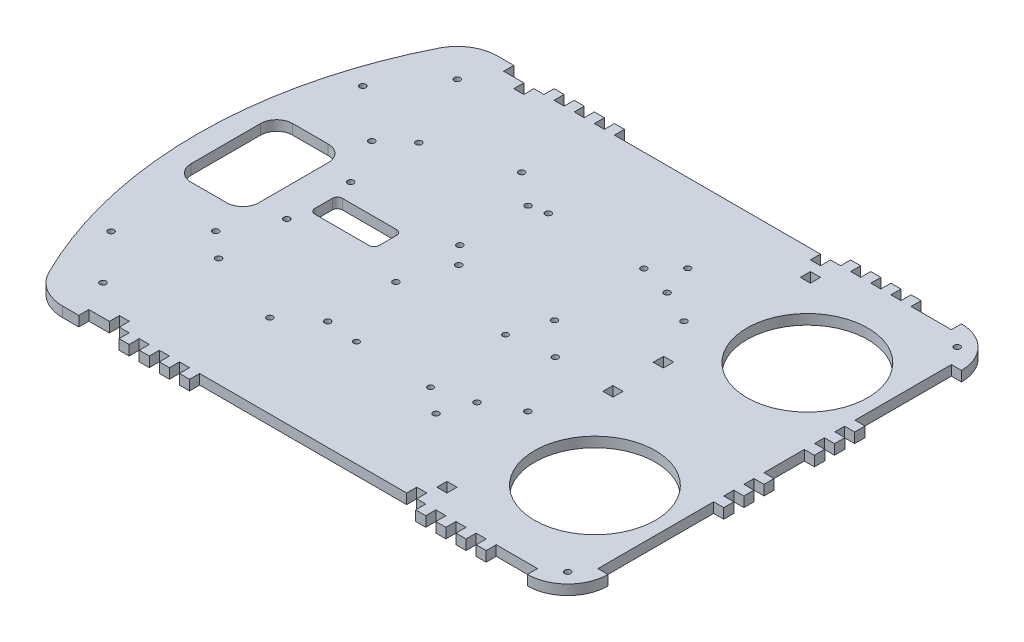
SolidWorks part; units mm, degrees
ref_plane "Front Plane" through (0, 0, 0) normal (0, 0, 1) x (1, 0, 0)
ref_plane "Top Plane" through (0, 0, 0) normal (0, 1, 0) x (1, 0, 0)
ref_plane "Right Plane" through (0, 0, 0) normal (1, 0, 0) x (0, 0, -1)
sketch "main_base_sketch" plane through (0, 0, 0) normal (0, 1, 0) x (1, 0, 0)
  line L1 (111.125, 92.7285) -> (111.125, 23.3533) construction
  line L2 (111.125, -38.1761) -> (111.125, 0) construction
  line L3 (111.125, -99.4864) -> (111.125, -136.4602) construction
  line L5 (111.125, 23.3533) -> (111.125, 0) construction
  line L7 (111.125, 92.7285) -> (111.125, 23.3533) construction
  line L9 (111.125, 0) -> (111.125, 23.3533) construction
  line L10 (111.125, 0) -> (111.125, -38.1761) construction
  line L11 (111.125, 0) -> (111.125, -38.1761) construction
  line L20 (-111.125, 0) -> (111.125, 0) construction
  line L22 (111.125, 130.8285) -> (117.475, 130.8285) construction
  line L24 (-94.9614, 130.8285) -> (-94.9614, 124.4785) construction
  line L25 (-94.9614, 124.4785) -> (-82.2614, 124.4785)
  line L26 (187.325, 130.8285) -> (187.325, 124.4785)
  line L27 (-95.6016, -142.8102) -> (111.125, -142.8102) construction
  line L28 (-95.6016, -142.8102) -> (-95.6016, -136.4602)
  line L29 (-95.6016, -136.4602) -> (-82.6643, -136.4602)
  line L30 (187.325, -142.8102) -> (187.325, -136.4602)
  line L32 (-94.9614, 130.8285) -> (-25.1114, 130.8285) construction
  line L33 (111.125, -142.8102) -> (187.325, -142.8102) construction
  line L34 (111.125, -136.4602) -> (111.125, -142.8102) construction
  line L36 (111.125, -136.4602) -> (111.125, -142.8102) construction
  line L37 (-56.8614, 130.8285) -> (-50.5114, 130.8285)
  line L38 (111.125, 12.7) -> (117.4276, 12.7)
  line L52 (111.125, 12.7) -> (111.125, 19.2555)
  line L53 (111.125, 23.3533) -> (111.125, 0) construction
  line L54 (111.125, 19.2555) -> (117.4276, 19.2555)
  line L55 (-94.9614, 130.8285) -> (-25.1114, 130.8285) construction
  line L58 (111.125, 124.4785) -> (111.125, 92.7285) construction
  line L61 (-95.6016, -142.8102) -> (111.125, -142.8102) construction
  line L62 (111.125, -99.4864) -> (111.125, -136.4602) construction
  line L63 (111.125, 130.8285) -> (117.475, 130.8285) construction
  line L64 (111.125, 124.4785) -> (111.125, 92.7285) construction
  line L65 (111.125, -142.8102) -> (187.325, -142.8102) construction
  line L66 (212.725, 105.4285) -> (212.725, -117.4102) construction
  line L67 (117.4276, 12.7) -> (117.4276, 19.2555)
  line L68 (111.125, -12.7) -> (117.475, -12.7)
  line L69 (111.125, -12.7) -> (111.125, -19.05)
  line L70 (111.125, -19.05) -> (117.475, -19.05)
  line L71 (117.475, -12.7) -> (117.475, -19.05)
  line L72 (111.125, 105.4285) -> (117.475, 105.4285)
  line L73 (111.125, 105.4285) -> (111.125, 111.7785)
  line L74 (111.125, 111.7785) -> (117.475, 111.7785)
  line L75 (117.475, 105.4285) -> (117.475, 111.7785)
  line L76 (111.125, -117.4102) -> (117.475, -117.4102)
  line L77 (111.125, -117.4102) -> (111.125, -123.7602)
  line L78 (111.125, -123.7602) -> (117.475, -123.7602)
  line L79 (117.475, -117.4102) -> (117.475, -123.7602)
  line L80 (212.725, 105.4285) -> (206.375, 105.4285)
  line L81 (212.725, 105.4285) -> (212.725, -117.4102) construction
  line L82 (212.725, -117.4102) -> (206.375, -117.4102)
  line L84 (-69.5614, 130.8285) -> (-63.2114, 130.8285)
  line L85 (-69.5614, 130.8285) -> (-69.5614, 124.4785)
  line L86 (-69.5614, 124.4785) -> (-63.2114, 124.4785) construction
  line L87 (-63.2114, 130.8285) -> (-63.2114, 124.4785)
  line L88 (-56.8614, 130.8285) -> (-56.8614, 124.4785)
  line L89 (-56.8614, 124.4785) -> (-50.5114, 124.4785) construction
  line L90 (-50.5114, 130.8285) -> (-50.5114, 124.4785)
  line L91 (-44.1614, 130.8285) -> (-37.8114, 130.8285)
  line L92 (-44.1614, 130.8285) -> (-44.1614, 124.4785)
  line L93 (-44.1614, 124.4785) -> (-37.8114, 124.4785) construction
  line L94 (-37.8114, 130.8285) -> (-37.8114, 124.4785)
  line L95 (-31.4614, 130.8285) -> (-25.1114, 130.8285)
  line L96 (-31.4614, 130.8285) -> (-31.4614, 124.4785)
  line L97 (-31.4614, 124.4785) -> (-25.1114, 124.4785) construction
  line L98 (-25.1114, 130.8285) -> (-25.1114, 124.4785)
  line L99 (-69.5614, 124.4785) -> (-63.2114, 124.4785) construction
  line L100 (-63.2114, 124.4785) -> (-56.8614, 124.4785)
  line L101 (-56.8614, 124.4785) -> (-50.5114, 124.4785) construction
  line L102 (-50.5114, 124.4785) -> (-44.1614, 124.4785)
  line L103 (-44.1614, 124.4785) -> (-37.8114, 124.4785) construction
  line L104 (-37.8114, 124.4785) -> (-31.4614, 124.4785)
  line L105 (-31.4614, 124.4785) -> (-25.1114, 124.4785) construction
  line L106 (-25.1114, 124.4785) -> (104.775, 124.4785)
  line L107 (149.225, 130.8285) -> (142.875, 130.8285)
  line L108 (161.925, 130.8285) -> (155.575, 130.8285)
  line L109 (161.925, 130.8285) -> (161.925, 124.4785)
  line L110 (161.925, 124.4785) -> (155.575, 124.4785) construction
  line L111 (155.575, 130.8285) -> (155.575, 124.4785)
  line L112 (149.225, 130.8285) -> (149.225, 124.4785)
  line L114 (142.875, 130.8285) -> (142.875, 124.4785)
  line L115 (136.525, 130.8285) -> (130.175, 130.8285)
  line L116 (136.525, 130.8285) -> (136.525, 124.4785)
  line L118 (130.175, 130.8285) -> (130.175, 124.4785)
  line L119 (123.825, 130.8285) -> (117.475, 130.8285) construction
  line L120 (123.825, 130.8285) -> (123.825, 124.4785)
  line L122 (117.475, 130.8285) -> (117.475, 124.4785) construction
  line L123 (117.475, 130.8285) -> (123.825, 130.8285) construction
  line L124 (206.375, 105.4285) -> (206.375, 44.6555)
  line L127 (117.475, 130.8285) -> (117.475, 124.4785) construction
  line L128 (117.475, 130.8285) -> (117.475, 124.4785) construction
  line L129 (145.8534, 124.4785) -> (130.175, 124.4785) [skipped]
  line L130 (149.225, 124.4785) -> (146.7264, 124.4785) [skipped]
  line L131 (123.825, 124.4785) -> (130.175, 124.4785)
  line L132 (136.525, 124.4785) -> (142.875, 124.4785)
  line L133 (149.225, 124.4785) -> (155.575, 124.4785)
  line L134 (161.925, 124.4785) -> (187.325, 124.4785)
  line L135 (133.0367, 124.4785) -> (117.475, 124.4785) [skipped]
  line L136 (123.825, 130.8285) -> (187.325, 130.8285) construction
  line L137 (117.475, 130.8285) -> (123.825, 130.8285) construction
  line L138 (123.825, 130.8285) -> (187.325, 130.8285) construction
  line L139 (-25.1114, 130.8285) -> (111.125, 130.8285) construction
  line L140 (-25.1114, 130.8285) -> (111.125, 130.8285) construction
  line L141 (111.125, 130.8285) -> (111.125, 124.4785) construction
  line L142 (111.125, 130.8285) -> (111.125, 124.4785) construction
  line L143 (123.825, 130.8285) -> (117.475, 130.8285)
  line L144 (117.475, 130.8285) -> (117.475, 124.4785)
  line L151 (206.375, -12.7) -> (212.725, -12.7)
  line L152 (206.375, -12.7) -> (206.375, -19.05) construction
  line L153 (206.375, -19.05) -> (212.725, -19.05)
  line L154 (212.725, -12.7) -> (212.725, -19.05)
  line L155 (206.375, -12.7) -> (206.375, -19.05) construction
  line L156 (206.375, -19.05) -> (206.375, -25.4)
  line L157 (206.375, 19.2555) -> (212.725, 19.2555)
  line L158 (212.725, 19.2555) -> (212.725, 12.7)
  line L159 (212.725, 12.7) -> (206.375, 12.7)
  line L160 (206.375, 24.1792) -> (206.375, 19.2555)
  line L161 (206.375, 12.7) -> (206.375, -12.7)
  line L162 (-70.2016, -136.4602) -> (-70.2016, -142.8102)
  line L163 (-70.2016, -142.8102) -> (-63.8516, -142.8102)
  line L164 (-63.8516, -142.8102) -> (-63.8516, -136.4602)
  line L165 (-70.2016, -136.4602) -> (-63.8516, -136.4602) construction
  line L166 (-63.8516, -136.4602) -> (-57.5016, -136.4602)
  line L167 (-57.5016, -142.8102) -> (-51.1516, -142.8102)
  line L168 (-57.5016, -136.4602) -> (-57.5016, -142.8102)
  line L169 (-51.1516, -142.8102) -> (-51.1516, -136.4602)
  line L170 (-44.8016, -142.8102) -> (-38.4516, -142.8102)
  line L171 (-44.8016, -136.4602) -> (-44.8016, -142.8102)
  line L172 (-38.4516, -142.8102) -> (-38.4516, -136.4602)
  line L173 (-32.1016, -142.8102) -> (-25.7516, -142.8102)
  line L174 (-32.1016, -136.4602) -> (-32.1016, -142.8102)
  line L175 (-25.7516, -142.8102) -> (-25.7516, -136.4602)
  line L176 (-57.5016, -136.4602) -> (-51.1516, -136.4602) construction
  line L177 (-51.1516, -136.4602) -> (-44.8016, -136.4602)
  line L178 (-44.8016, -136.4602) -> (-38.4516, -136.4602) construction
  line L179 (-38.4516, -136.4602) -> (-32.1016, -136.4602)
  line L180 (-32.1016, -136.4602) -> (-25.7516, -136.4602) construction
  line L181 (-25.7516, -136.4602) -> (104.775, -136.4602)
  line L182 (161.2847, -136.4602) -> (161.2847, -142.8102)
  line L183 (161.2847, -142.8102) -> (154.9347, -142.8102)
  line L184 (154.9347, -142.8102) -> (154.9347, -136.4602)
  line L185 (148.5847, -136.4602) -> (148.5847, -142.8102)
  line L186 (148.5847, -142.8102) -> (142.2347, -142.8102)
  line L187 (142.2347, -142.8102) -> (142.2347, -136.4602)
  line L188 (135.8847, -136.4602) -> (135.8847, -142.8102)
  line L189 (135.8847, -142.8102) -> (129.5347, -142.8102)
  line L190 (129.5347, -142.8102) -> (129.5347, -136.4602)
  line L191 (123.1847, -136.4602) -> (123.1847, -142.8102)
  line L192 (123.1847, -142.8102) -> (116.8347, -142.8102)
  line L193 (116.8347, -142.8102) -> (116.8347, -136.4602)
  line L194 (154.9347, -136.4602) -> (161.2847, -136.4602) construction
  line L195 (161.2847, -136.4602) -> (187.325, -136.4602)
  line L196 (142.2347, -136.4602) -> (148.5847, -136.4602) construction
  line L197 (148.5847, -136.4602) -> (154.9347, -136.4602)
  line L198 (129.5347, -136.4602) -> (135.8847, -136.4602) construction
  line L199 (135.8847, -136.4602) -> (142.2347, -136.4602)
  line L200 (116.8347, -136.4602) -> (123.1847, -136.4602) construction
  line L201 (123.1847, -136.4602) -> (129.5347, -136.4602)
  line L202 (212.725, 25.4) -> (206.375, 25.4)
  line L203 (212.725, 31.9555) -> (212.725, 25.4)
  line L204 (206.375, 31.9555) -> (212.725, 31.9555)
  line L205 (212.725, 38.1) -> (206.375, 38.1)
  line L206 (212.725, 44.6555) -> (212.725, 38.1)
  line L207 (206.375, 44.6555) -> (212.725, 44.6555)
  line L208 (206.375, 31.9555) -> (206.375, 25.4) construction
  line L209 (206.375, 25.4) -> (206.375, 24.1792)
  line L210 (206.375, 44.6555) -> (206.375, 38.1) construction
  line L211 (206.375, 38.1) -> (206.375, 31.9555)
  line L212 (206.375, -31.75) -> (212.725, -31.75)
  line L213 (212.725, -25.4) -> (212.725, -31.75)
  line L214 (206.375, -25.4) -> (212.725, -25.4)
  line L215 (206.375, -44.45) -> (212.725, -44.45)
  line L216 (212.725, -38.1) -> (212.725, -44.45)
  line L217 (206.375, -38.1) -> (212.725, -38.1)
  line L218 (206.375, -25.4) -> (206.375, -31.75) construction
  line L219 (206.375, -31.75) -> (206.375, -38.1)
  line L220 (206.375, -38.1) -> (206.375, -44.45) construction
  line L221 (206.375, -44.45) -> (206.375, -117.4102)
  line L225 (-95.5505, 130.8285) -> (-157.7358, 130.8285) construction
  line L229 (-132.8963, 29.3852) -> (-110.4973, 29.3852)
  line L230 (-143.0563, 19.2252) -> (-143.0563, -24.5291)
  line L231 (-132.8963, -34.6891) -> (-110.4973, -34.6891)
  line L238 (-100.3373, 19.2252) -> (-100.3373, -24.5291)
  line L248 (-94.9614, 130.8285) -> (-95.5505, 130.8285) construction
  line L254 (-94.9614, 130.8285) -> (-95.5505, 130.8285) construction
  line L257 (-94.9614, 130.8285) -> (-105.2412, 130.8285)
  line L258 (-95.5505, 130.8285) -> (-94.9614, 130.8285) construction
  line L259 (-95.6016, -142.8102) -> (-105.7982, -142.8102)
  line L260 (-94.9614, 124.4785) -> (-94.9614, 130.8285)
  line L261 (-94.9614, 130.8285) -> (-95.5505, 130.8285) construction
  line L262 (-82.2614, 124.4785) -> (-75.9114, 124.4785) construction
  line L263 (-82.2614, 124.4785) -> (-75.9114, 124.4785) construction
  line L264 (-82.2614, 124.4785) -> (-82.2614, 118.1285)
  line L265 (-82.2614, 118.1285) -> (-75.9114, 118.1285)
  line L266 (-75.9114, 124.4785) -> (-75.9114, 118.1285)
  line L267 (-97.1554, -142.8102) -> (-95.6016, -142.8102) construction
  line L269 (-75.9114, 124.4785) -> (-69.5614, 124.4785)
  line L270 (104.775, 124.4785) -> (111.125, 124.4785) construction
  line L271 (111.125, 124.4785) -> (104.775, 124.4785) construction
  line L272 (111.125, 124.4785) -> (111.125, 118.1285)
  line L274 (111.125, 118.1285) -> (104.775, 118.1285)
  line L280 (104.775, 124.4785) -> (104.775, 118.1285)
  line L281 (111.125, 124.4785) -> (117.475, 124.4785)
  line L282 (104.775, -136.4602) -> (111.125, -136.4602) construction
  line L285 (111.125, -136.4602) -> (104.775, -136.4602) construction
  line L286 (111.125, -136.4602) -> (111.125, -130.1018)
  line L289 (111.125, -130.1018) -> (104.775, -130.1018)
  line L291 (104.775, -136.4602) -> (104.775, -130.1018)
  line L292 (111.125, -136.4602) -> (116.8347, -136.4602)
  line L293 (-82.6643, -136.4602) -> (-76.4089, -136.4602) construction
  line L294 (-94.9614, 130.8285) -> (-95.5505, 130.8285) construction
  line L295 (-157.7358, 130.8285) -> (-157.7358, -142.8102) construction
  line L296 (-157.7358, -142.8102) -> (-97.1554, -142.8102) construction
  line L297 (-95.5505, 130.8285) -> (-157.7358, 130.8285) construction
  line L298 (-82.6643, -136.4602) -> (-76.4089, -136.4602) construction
  line L299 (-82.6643, -136.4602) -> (-82.6643, -130.1018)
  line L300 (-82.6643, -130.1018) -> (-76.4089, -130.1018)
  line L301 (-76.4089, -136.4602) -> (-76.4089, -130.1018)
  line L302 (-76.4089, -136.4602) -> (-70.2016, -136.4602)
  arc A34 (212.725, -117.4102) -> (187.325, -142.8102) centre (187.325, -117.4102) cw
  arc A35 (212.725, 105.4285) -> (187.325, 130.8285) centre (187.325, 105.4285) ccw
  circle A37 centre (160.02, 60.9785) radius 38.1
  circle A38 centre (160.02, -72.9602) radius 38.1
  arc A41 (-127.9188, 116.8691) -> (-128.5327, -128.7374) centre (116.7138, -6.5464) ccw
  arc A42 (-127.9188, 116.8691) -> (-105.2412, 130.8285) centre (-105.2412, 105.4285) cw
  arc A43 (-128.5327, -128.7374) -> (-105.7982, -142.8102) centre (-105.7982, -117.4102) ccw
  circle A44 centre (-131.2964, 71.9636) radius 1.905
  circle A45 centre (-131.2964, -86.7864) radius 1.905
  circle A46 centre (198.6177, 116.8691) radius 1.905
  circle A47 centre (198.6177, -128.7374) radius 1.905
  circle A50 centre (-105.2412, 105.4285) radius 1.905
  arc A51 (-110.4973, -34.6891) -> (-100.3373, -24.5291) centre (-110.4973, -24.5291) ccw
  arc A52 (-143.0563, -24.5291) -> (-132.8963, -34.6891) centre (-132.8963, -24.5291) ccw
  arc A53 (-132.8963, 29.3852) -> (-143.0563, 19.2252) centre (-132.8963, 19.2252) ccw
  arc A54 (-110.4973, 29.3852) -> (-100.3373, 19.2252) centre (-110.4973, 19.2252) cw
  circle A55 centre (-105.7982, -117.4102) radius 1.905
  point P16 (-120.3614, 130.8285)
  point P19 (212.725, -142.8102)
  point P46 (-121.0016, -142.8102)
  point P123 (0, 0)
  dimension "D7" = 63.5
  dimension "D12" = 25.4
  dimension "D13" = 25.4
  dimension "D21" = 63.5
  dimension "D24" = 76.2
  dimension "D26" = 76.2
  dimension "D14" = 25.4
  dimension "D30" = 3.81
  dimension "D31" = 6.35
  dimension "D4" = 10.16
  dimension "D8" = 4
  dimension "D11" = 4
  dimension "D19" = 6.35
  dimension "D20" = 6.35
  dimension "D27" = 10.2799
  dimension "D28" = 10.1966
  dimension "D29" = 6.5555
  dimension "D32" = 6.35
  dimension "D33" = 6.35
  dimension "D36" = 6.35
  dimension "D57" = 38.1
  dimension "D58" = 6.35
  dimension "D59" = 101.6
  dimension "D60" = 6.3026
  dimension "D61" = 12.7
  dimension "D62" = 12.7
  dimension "D63" = 6.35
  dimension "D64" = 6.35
  dimension "D65" = 6.35
  dimension "D66" = 6.35
  dimension "D67" = 12.7
  dimension "D68" = 12.7
  dimension "D69" = 6.35
  dimension "D70" = 6.35
  dimension "D71" = 4
  dimension "D72" = 6.35
  dimension "D73" = 6.35
  dimension "D74" = 6.35
  dimension "D76" = 3
  dimension "D77" = 3
  dimension "D78" = 6.3585
  dimension "D79" = 282.9266
  dimension "D75" = 4
extrude "main_base" add sketch "main_base_sketch" along normal blind 6.35
sketch "Sketch1" plane through (0, 6.35, 0) normal (0, 1, 0) x (1, 0, 0)
  line L20 (-111.125, -4.4655) -> (111.125, -4.4655) construction
  line L39 (-42.259, -13.1472) -> (-76.4089, -13.1472)
  line L40 (-39.084, -9.9722) -> (-39.084, 1.0411)
  line L41 (-42.259, 4.2161) -> (-76.4089, 4.2161)
  line L42 (-79.5839, -9.9722) -> (-79.5839, 1.0411)
  line L43 (-39.084, -13.1472) -> (-79.5839, 4.2161) construction
  line L44 (-39.084, 4.2161) -> (-79.5839, -13.1472) construction
  line L45 (61.595, 59.0345) -> (93.345, 59.0345) construction
  line L46 (61.595, 59.0345) -> (61.595, -67.9655) construction
  line L47 (61.595, -67.9655) -> (93.345, -67.9655) construction
  line L48 (93.345, 59.0345) -> (93.345, -67.9655) construction
  line L49 (61.595, 59.0345) -> (93.345, -67.9655) construction
  line L50 (61.595, -67.9655) -> (93.345, 59.0345) construction
  circle A0 centre (-82.6643, 58.6916) radius 1.905
  circle A1 centre (-13.8303, 58.6916) radius 1.905
  arc A2 (-76.4089, -13.1472) -> (-79.5839, -9.9722) centre (-76.4089, -9.9722) cw
  arc A3 (-42.259, -13.1472) -> (-39.084, -9.9722) centre (-42.259, -9.9722) ccw
  arc A4 (-39.084, 1.0411) -> (-42.259, 4.2161) centre (-42.259, 1.0411) ccw
  arc A5 (-76.4089, 4.2161) -> (-79.5839, 1.0411) centre (-76.4089, 1.0411) ccw
  circle A10 centre (-3.2843, 60.9395) radius 1.905
  circle A11 centre (-13.8303, 15.6894) radius 1.905
  circle A12 centre (-3.2843, 4.4753) radius 1.905
  circle A13 centre (-82.6643, 15.6894) radius 1.905
  circle A14 centre (-82.6643, -24.6204) radius 1.905
  circle A15 centre (-13.8303, -24.6204) radius 1.905
  circle A16 centre (-82.6643, -67.6226) radius 1.905
  circle A17 centre (-13.8303, -67.6226) radius 1.905
  circle A18 centre (6.29, -69.6017) radius 1.796
  circle A19 centre (54.55, -71.1892) radius 1.796
  circle A20 centre (49.47, -18.8017) radius 1.796
  circle A21 centre (57.0407, 4.4753) radius 1.905
  circle A22 centre (57.0407, 60.9395) radius 1.905
  circle A23 centre (-98.425, 44.7683) radius 1.905
  circle A24 centre (-34.0871, 74.9095) radius 1.905
  circle A25 centre (70.6863, 74.9095) radius 1.905
  circle A26 centre (98.425, 44.7683) radius 1.905
  circle A27 centre (98.425, -53.6993) radius 1.905
  circle A28 centre (70.6863, -83.8405) radius 1.905
  circle A29 centre (-34.0871, -83.8405) radius 1.905
  circle A30 centre (-98.425, -53.6993) radius 1.905
  circle A31 centre (77.47, -64.7905) radius 1.905
  circle A32 centre (77.47, 55.0657) radius 1.905
  circle A33 centre (77.47, -15.4193) radius 1.905
  point P40 (-59.334, -4.4655)
  point P111 (77.47, -67.9655)
  point P113 (77.47, -4.4655)
  dimension "D1" = 3.175
  dimension "D40" = 3.81
  dimension "D41" = 3.81
  dimension "D42" = 3.81
  dimension "D43" = 3.592
  dimension "D44" = 3.592
  dimension "D45" = 3.592
  dimension "D9" = 40.4999
  dimension "D10" = 17.3633
  dimension "D15" = 104.7734
  dimension "D24" = 60.325
  dimension "D33" = 68.834
  dimension "D35" = 20.1549
  dimension "D36" = 20.1549
  dimension "D37" = 35.7997
  dimension "D46" = 1.5875
  dimension "D47" = 48.26
  dimension "D48" = 127
  dimension "D49" = 31.75
  dimension "D51" = 3.175
  dimension "D52" = 3.9688
  dimension "D53" = 70.485
  dimension "D54" = 56.4642
  dimension "D55" = 23.277
  dimension "D56" = 74.077
extrude "Cut-Extrude1" cut sketch "Sketch1" against normal through all
